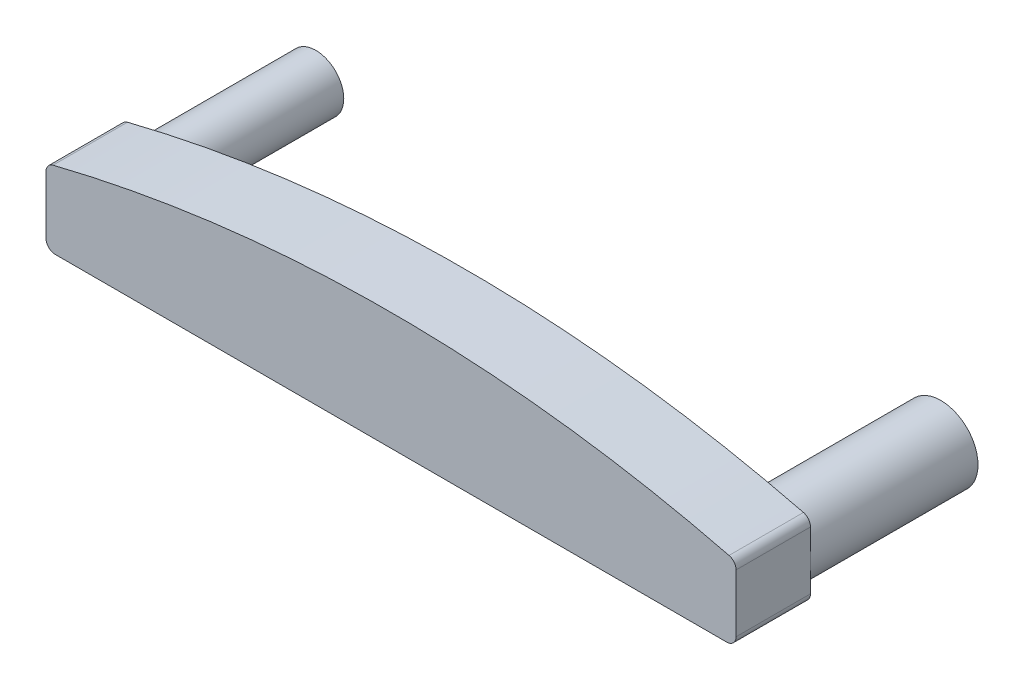
SolidWorks part; units mm, degrees
material "PLA 100% Infill"
ref_plane "Front Plane" through (0, 0, 0) normal (0, 0, 1) x (1, 0, 0)
ref_plane "Top Plane" through (0, 0, 0) normal (0, 1, 0) x (1, 0, 0)
ref_plane "Right Plane" through (0, 0, 0) normal (1, 0, 0) x (0, 0, -1)
sketch "Sketch1" plane through (0, 0, 0) normal (0, 0, 1) x (1, 0, 0)
  line L0 (0, -2) -> (37.08, -2) construction
  line L1 (0, 0) -> (37.08, 0) construction
  line L2 (0, 0) -> (0, -4)
  line L3 (0, -4) -> (37.08, -4)
  line L4 (37.08, 0) -> (37.08, -4)
  line L5 (36.2347, -2.6667) -> (33.9253, -2.6667)
  line L6 (33.9253, -2.6667) -> (35.08, -0.6667)
  line L7 (35.08, -0.6667) -> (36.2347, -2.6667)
  line L8 (35.08, -0.6667) -> (35.08, -2.6667) construction
  line L10 (35.6574, -1.6667) -> (33.9253, -2.6667) construction
  circle A0 centre (1.5, -2) radius 1.5
  circle A1 centre (35.08, -2) radius 2
  arc A3 (37.08, 0) -> (0, 0) centre (18.54, -72.6723) ccw
  arc A4 (37.08, -4) -> (0, -4) centre (18.54, 68.6723) cw construction
  point P18 (35.08, -2)
  dimension "D2" = 3
  dimension "D3" = 4
  dimension "D5" = 2
  dimension "D6" = 150
  dimension "D1" = 4
  dimension "D4" = 33.58
extrude "Boss-Extrude1" add sketch "Sketch1" along normal blind 4 contours L4 L3 L2 A3
extrude "Boss-Extrude2" add sketch "Sketch1<3>" against normal blind 9 contours L0 A1 | A1 L0 | A0 L0 | L0 A0 | L5 L6 L7 region at (1.5, -2, 0) region at (36.4542, -3.3742, 0)
sketch "Sketch1<3>" plane through (0, 0, 0) normal (0, 0, 1) x (1, 0, 0) same geometry as "Sketch1"
ref_plane "Plane1" [suppressed] through (0, 0, -19) normal (0, 0, -1) x (-1, 0, 0)
fillet "Fillet1" radius 0.5 4 edges at (0, -4, 2) (37.08, -4, 2) (37.08, 0, 2) (0, 0, 2)
